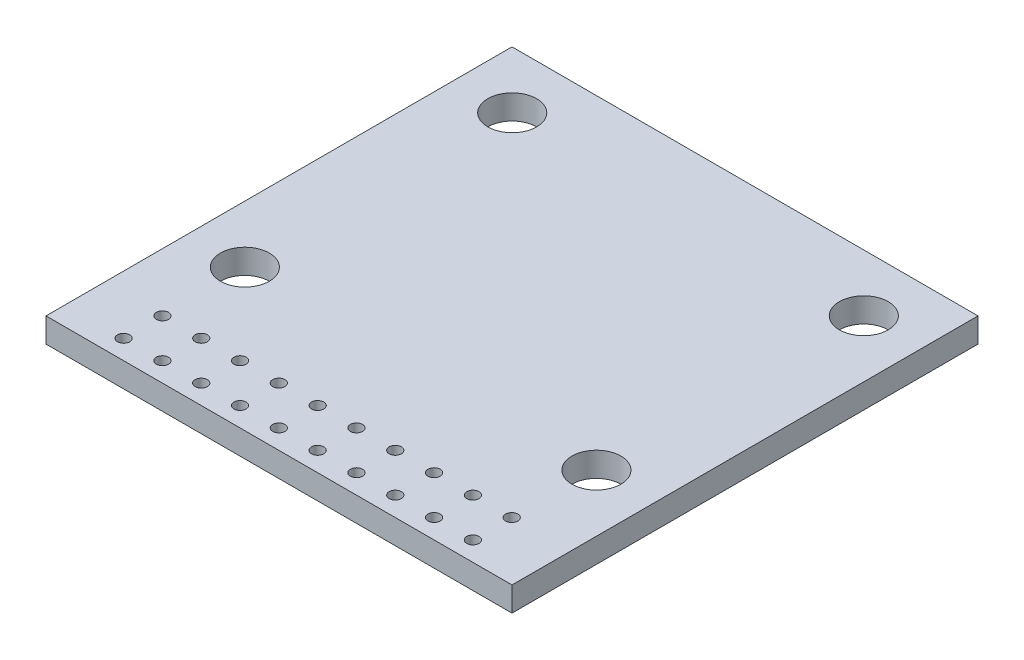
SolidWorks part; units mm, degrees
ref_plane "Alzado" through (0, 0, 0) normal (0, 0, 1) x (1, 0, 0)
ref_plane "Planta" through (0, 0, 0) normal (0, 1, 0) x (1, 0, 0)
ref_plane "Vista lateral" through (0, 0, 0) normal (1, 0, 0) x (0, 0, -1)
sketch "Croquis1" plane through (0, 0, 0) normal (0, 1, 0) x (1, 0, 0)
  line L1 (-15.25, -15.25) -> (15.25, -15.25)
  line L2 (-15.25, -15.25) -> (-15.25, 15.25)
  line L3 (-15.25, 15.25) -> (15.25, 15.25)
  line L4 (15.25, -15.25) -> (15.25, 15.25)
  line L5 (-15.25, -15.25) -> (15.25, 15.25) construction
  line L6 (-15.25, 15.25) -> (15.25, -15.25) construction
  point P0 (0, 0)
  dimension "D1" = 30.5
  dimension "D2" = 30.5
extrude "Saliente-Extruir1" add sketch "Croquis1" along normal blind 1.6
sketch "Croquis2" plane through (0, 1.6, 0) normal (0, 1, 0) x (1, 0, 0)
  line L0 (0, 0) -> (0, 25.1156) construction
  circle A0 centre (-11.505, 11.52) radius 1.6
  circle A1 centre (11.505, 11.52) radius 1.6
  circle A2 centre (11.505, -5.98) radius 1.6
  circle A3 centre (-11.505, -5.98) radius 1.6
  point P10 (0, 0)
  point P13 (0, 0)
  dimension "D1" = 3.73
  dimension "D2" = 3.2
  dimension "D4" = 3.2
  dimension "D6" = 3.2
  dimension "D3" = 23.01
  dimension "D5" = 17.5
extrude "Cortar-Extruir3" cut sketch "Croquis2" against normal through all
sketch "Croquis3" plane through (0, 1.6, 0) normal (0, 1, 0) x (1, 0, 0)
  line L0 (-15.9747, -12.6506) -> (16.6004, -12.6506) construction
  circle A0 centre (-11.44, -13.98) radius 0.4
  circle A1 centre (-8.9, -13.98) radius 0.4
  circle A2 centre (-6.36, -13.98) radius 0.4
  circle A3 centre (-3.82, -13.98) radius 0.4
  circle A4 centre (-1.28, -13.98) radius 0.4
  circle A5 centre (1.26, -13.98) radius 0.4
  circle A6 centre (3.8, -13.98) radius 0.4
  circle A7 centre (6.34, -13.98) radius 0.4
  circle A8 centre (8.88, -13.98) radius 0.4
  circle A9 centre (11.42, -13.98) radius 0.4
  circle A10 centre (-11.44, -11.44) radius 0.4
  circle A11 centre (-8.9, -11.44) radius 0.4
  circle A12 centre (-6.36, -11.44) radius 0.4
  circle A13 centre (-3.82, -11.44) radius 0.4
  circle A14 centre (-1.28, -11.44) radius 0.4
  circle A15 centre (1.26, -11.44) radius 0.4
  circle A16 centre (3.8, -11.44) radius 0.4
  circle A17 centre (6.34, -11.44) radius 0.4
  circle A18 centre (8.88, -11.44) radius 0.4
  circle A19 centre (11.42, -11.44) radius 0.4
  dimension "D1" = 0.8
  dimension "D5" = 0.8
  dimension "D2" = 1.27
  dimension "D3" = 3.81
  dimension "D6" = 2.54
  dimension "D4" = 10
  dimension "D7" = 10
extrude "Cortar-Extruir4" cut sketch "Croquis3" against normal through all
sketch "Croquis4" plane through (0, 1.6, 0) normal (0, 1, 0) x (1, 0, 0)
  line L0 (-2.51, 2.6) -> (2.49, 2.6) construction
  line L1 (-2.51, 0.1) -> (2.49, 0.1)
  line L2 (-2.51, 0.1) -> (-2.51, 5.1)
  line L3 (-2.51, 5.1) -> (2.49, 5.1)
  line L4 (2.49, 0.1) -> (2.49, 5.1)
  line L5 (-0.01, 0.1) -> (-0.01, 5.1) construction
  line L6 (15.25, 15.25) -> (-15.25, 15.25) construction
  line L7 (-15.25, 15.25) -> (-15.25, -15.25) construction
  point P8 (-0.01, 2.6)
  point P13 (-13.2084, 5.8784)
  dimension "D1" = 5
  dimension "D2" = 5
  dimension "D3" = 12.65
  dimension "D4" = 15.24
